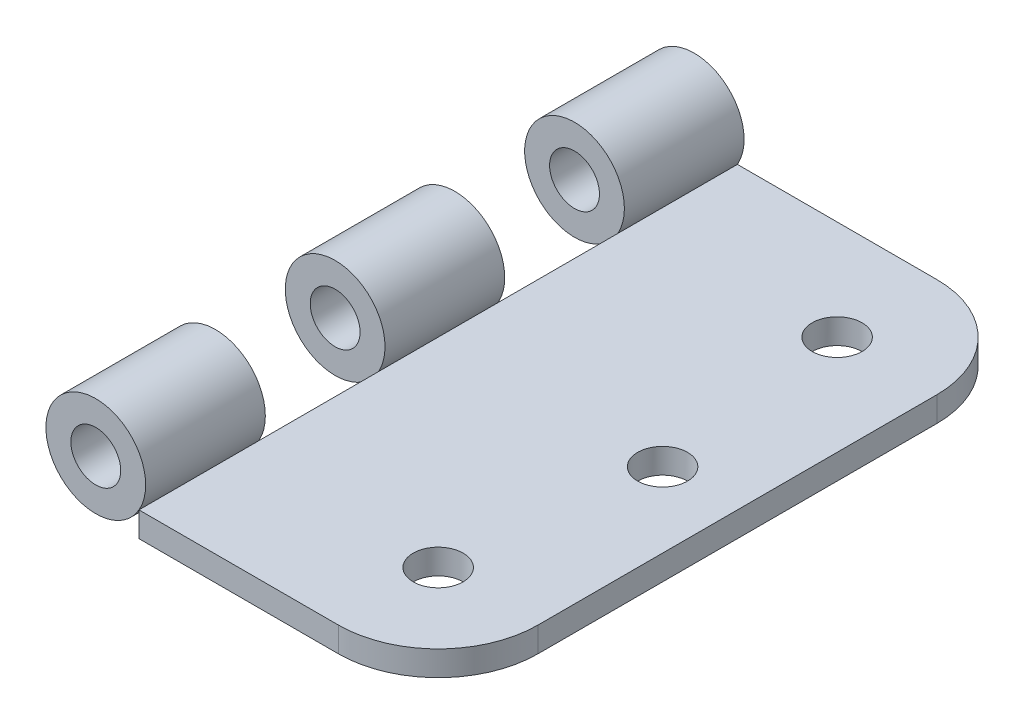
SolidWorks part; units mm, degrees
ref_plane "Front Plane" through (0, 0, 0) normal (0, 0, 1) x (1, 0, 0)
ref_plane "Top Plane" through (0, 0, 0) normal (0, 1, 0) x (1, 0, 0)
ref_plane "Right Plane" through (0, 0, 0) normal (1, 0, 0) x (0, 0, -1)
sketch "Sketch1" plane through (0, 0, 0) normal (0, 1, 0) x (1, 0, 0)
  line L1 (0, 0) -> (38.1, 0)
  line L2 (0, 0) -> (0, 76.2)
  line L3 (0, 76.2) -> (38.1, 76.2)
  line L4 (38.1, 0) -> (38.1, 76.2)
  dimension "D1" = 38.1
  dimension "D2" = 76.2
extrude "Boss-Extrude1" add sketch "Sketch1" along normal blind 3.175
sketch "Sketch2" plane through (0, 3.175, 0) normal (0, 1, 0) x (-1, 0, 0)
  line L0 (-38.1, 0) -> (-38.1, -76.2) construction
  line L1 (-38.1, -38.1) -> (0, -38.1) construction
  line L2 (0, -76.2) -> (0, 0) construction
  circle A0 centre (-25.4, -63.5) radius 3.175
  circle A1 centre (-28.575, -38.1) radius 3.175
  circle A2 centre (-25.4, -12.7) radius 3.175
  dimension "D4" = 6.35
  dimension "D3" = 25.4
  dimension "D1" = 9.525
  dimension "D2" = 12.7
extrude "Cut-Extrude1" cut sketch "Sketch2" against normal up to next
fillet "Fillet1" radius 12.7 2 edges at (38.1, 1.5875, 0) (38.1, 1.5875, -76.2)
sketch "Sketch3" plane through (0, 0, 0) normal (0, 0, 1) x (1, 0, 0)
  line L0 (0, 0) -> (25.4, 0) construction
  circle A0 centre (-5.4993, 6.35) radius 6.35
  circle A1 centre (-5.4993, 6.35) radius 3.175
  dimension "D1" = 12.7
  dimension "D2" = 6.35
extrude "Boss-Extrude2" add sketch "Sketch3" against normal blind 15.24 separate body
extrude "Boss-Extrude3" add sketch "Sketch3<2>" against normal blind 15.24 from offset 30.48 separate body offset against normal yes
sketch "Sketch3<2>" plane through (0, 0, 0) normal (0, 0, 1) x (1, 0, 0) same geometry as "Sketch3"
extrude "Boss-Extrude4" add sketch "Sketch3<3>" against normal blind 15.24 from offset 60.96 separate body offset against normal yes
sketch "Sketch3<3>" plane through (0, 0, 0) normal (0, 0, 1) x (1, 0, 0) same geometry as "Sketch3"
